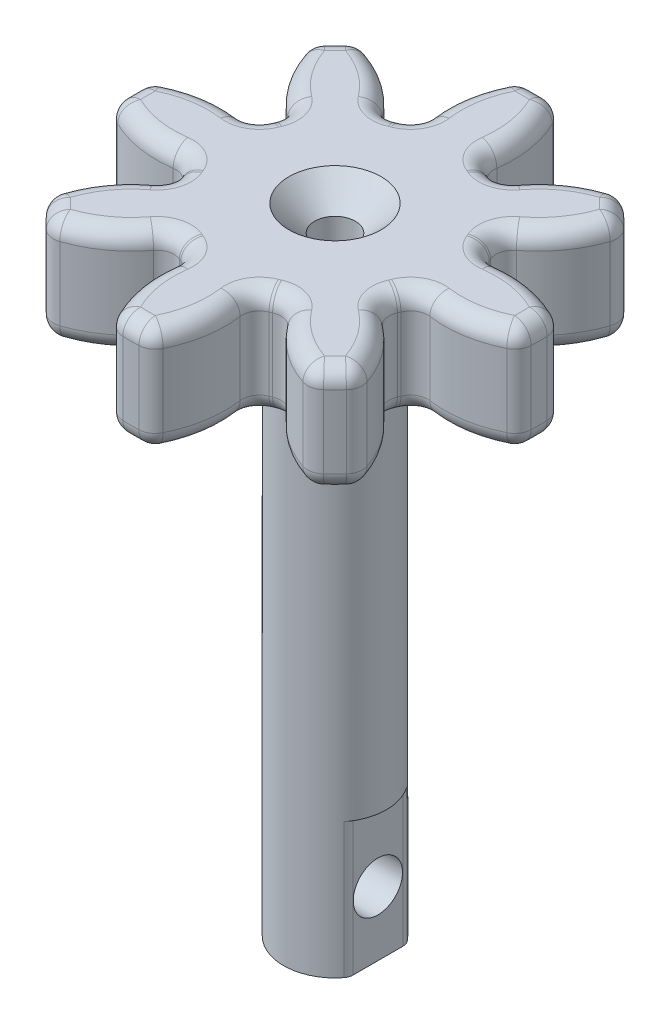
SolidWorks part; units mm, degrees
ref_plane "Front Plane" through (0, 0, 0) normal (0, 0, 1) x (1, 0, 0)
ref_plane "Top Plane" through (0, 0, 0) normal (0, 1, 0) x (1, 0, 0)
ref_plane "Right Plane" through (0, 0, 0) normal (1, 0, 0) x (0, 0, -1)
sketch "Sketch2" plane through (0, 0, 0) normal (0, 1, 0) x (1, 0, 0)
  line L0 (1.5575, 7.479) -> (0, 0) construction
  line L1 (1.5575, 7.479) -> (1.9249, 4.9409) construction
  line L2 (-1.4311, 5.3411) -> (0, 0) construction
  line L3 (0, 0) -> (1.4311, 5.3411) construction
  line L4 (-6.7384, 6.7384) -> (0, 0) construction
  line L5 (0, 0) -> (-2.7648, 4.7887) construction
  circle A0 centre (0, 0) radius 5.5295 construction
  circle A1 centre (0, 0) radius 9.5295 construction
  arc A2 (1.4311, 5.3411) -> (0.8301, 9.4933) centre (-3.7048, 6.7173) ccw
  arc A3 (-1.4311, 5.3411) -> (-0.8301, 9.4933) centre (3.7048, 6.7173) cw
  arc A4 (0.8301, 9.4933) -> (-0.8301, 9.4933) centre (0, 0) ccw
  arc A5 (1.4311, 5.3411) -> (2.7648, 4.7887) centre (0, 0) cw
  arc A6 (4.7887, 2.7648) -> (5.3411, 1.4311) centre (0, 0) cw
  arc A7 (4.7887, 2.7648) -> (7.2997, 6.1258) centre (2.1302, 7.3695) ccw
  arc A8 (7.2997, 6.1258) -> (6.1258, 7.2997) centre (0, 0) ccw
  arc A9 (2.7648, 4.7887) -> (6.1258, 7.2997) centre (7.3695, 2.1302) cw
  arc A10 (5.3411, -1.4311) -> (4.7887, -2.7648) centre (0, 0) cw
  arc A11 (5.3411, -1.4311) -> (9.4933, -0.8301) centre (6.7173, 3.7048) ccw
  arc A12 (9.4933, -0.8301) -> (9.4933, 0.8301) centre (0, 0) ccw
  arc A13 (5.3411, 1.4311) -> (9.4933, 0.8301) centre (6.7173, -3.7048) cw
  arc A14 (2.7648, -4.7887) -> (1.4311, -5.3411) centre (0, 0) cw
  arc A15 (2.7648, -4.7887) -> (6.1258, -7.2997) centre (7.3695, -2.1302) ccw
  arc A16 (6.1258, -7.2997) -> (7.2997, -6.1258) centre (0, 0) ccw
  arc A17 (4.7887, -2.7648) -> (7.2997, -6.1258) centre (2.1302, -7.3695) cw
  arc A18 (-1.4311, -5.3411) -> (-2.7648, -4.7887) centre (0, 0) cw
  arc A19 (-1.4311, -5.3411) -> (-0.8301, -9.4933) centre (3.7048, -6.7173) ccw
  arc A20 (-0.8301, -9.4933) -> (0.8301, -9.4933) centre (0, 0) ccw
  arc A21 (1.4311, -5.3411) -> (0.8301, -9.4933) centre (-3.7048, -6.7173) cw
  arc A22 (-4.7887, -2.7648) -> (-5.3411, -1.4311) centre (0, 0) cw
  arc A23 (-4.7887, -2.7648) -> (-7.2997, -6.1258) centre (-2.1302, -7.3695) ccw
  arc A24 (-7.2997, -6.1258) -> (-6.1258, -7.2997) centre (0, 0) ccw
  arc A25 (-2.7648, -4.7887) -> (-6.1258, -7.2997) centre (-7.3695, -2.1302) cw
  arc A26 (-5.3411, 1.4311) -> (-4.7887, 2.7648) centre (0, 0) cw
  arc A27 (-5.3411, 1.4311) -> (-9.4933, 0.8301) centre (-6.7173, -3.7048) ccw
  arc A28 (-9.4933, 0.8301) -> (-9.4933, -0.8301) centre (0, 0) ccw
  arc A29 (-5.3411, -1.4311) -> (-9.4933, -0.8301) centre (-6.7173, 3.7048) cw
  arc A30 (-2.7648, 4.7887) -> (-1.4311, 5.3411) centre (0, 0) cw
  arc A31 (-2.7648, 4.7887) -> (-6.1258, 7.2997) centre (-7.3695, 2.1302) ccw
  arc A32 (-6.1258, 7.2997) -> (-7.2997, 6.1258) centre (0, 0) ccw
  arc A33 (-4.7887, 2.7648) -> (-7.2997, 6.1258) centre (-2.1302, 7.3695) cw
  arc A34 (6.3897, 4.1871) -> (1.5575, 7.479) centre (0, 0) ccw construction
  arc A35 (-1.0542, 3.9343) -> (-2.0366, 3.5274) centre (0, 0) ccw construction
  arc A36 (-2.0366, 3.5274) -> (-2.8801, 2.8801) centre (0, 0) ccw construction
  point P12 (0, 9.5295)
  point P68 (0, 0)
  dimension "D2" = 4
  dimension "D1" = 20
  dimension "D4" = 6
  dimension "D3" = 8
extrude "Boss-Extrude1" add sketch "Sketch2" along normal blind 5
fillet "Fillet3" radius 0.8 96 edges at (1.4311, 2.5, -5.3411) (0.8301, 2.5, -9.4933) (-0.8301, 2.5, -9.4933) (-1.4311, 2.5, -5.3411) (-2.7648, 2.5, -4.7887) (-6.1258, 2.5, -7.2997) (-7.2997, 2.5, -6.1258) (-4.7887, 2.5, -2.7648) (-5.3411, 2.5, -1.4311) (-9.4933, 2.5, -0.8301) (-9.4933, 2.5, 0.8301) (-5.3411, 2.5, 1.4311) (-4.7887, 2.5, 2.7648) (-7.2997, 2.5, 6.1258) (-6.1258, 2.5, 7.2997) (-2.7648, 2.5, 4.7887) (-1.4311, 2.5, 5.3411) (-0.8301, 2.5, 9.4933) (0.8301, 2.5, 9.4933) (1.4311, 2.5, 5.3411) (2.7648, 2.5, 4.7887) (6.1258, 2.5, 7.2997) (7.2997, 2.5, 6.1258) (4.7887, 2.5, 2.7648) (5.3411, 2.5, 1.4311) (9.4933, 2.5, 0.8301) (9.4933, 2.5, -0.8301) (5.3411, 2.5, -1.4311) (4.7887, 2.5, -2.7648) (7.2997, 2.5, -6.1258) (6.1258, 2.5, -7.2997) (2.7648, 2.5, -4.7887) (4.1871, 5, -6.3897) (6.7384, 5, -6.7384) (6.3897, 5, -4.1871) (5.1086, 5, -2.1161) (7.479, 5, -1.5575) (9.5295, 5, 0) (7.479, 5, 1.5575) (5.1086, 5, 2.1161) (6.3897, 5, 4.1871) (6.7384, 5, 6.7384) (4.1871, 5, 6.3897) (2.1161, 5, 5.1086) (1.5575, 5, 7.479) (0, 5, 9.5295) (-1.5575, 5, 7.479) (-2.1161, 5, 5.1086) (-4.1871, 5, 6.3897) (-6.7384, 5, 6.7384) (-6.3897, 5, 4.1871) (-5.1086, 5, 2.1161) (-7.479, 5, 1.5575) (-9.5295, 5, 0) (-7.479, 5, -1.5575) (-5.1086, 5, -2.1161) (-6.3897, 5, -4.1871) (-6.7384, 5, -6.7384) (-4.1871, 5, -6.3897) (-2.1161, 5, -5.1086) (-1.5575, 5, -7.479) (0, 5, -9.5295) (1.5575, 5, -7.479) (2.1161, 5, -5.1086) (4.1871, 0, -6.3897) (6.7384, 0, -6.7384) (6.3897, 0, -4.1871) (5.1086, 0, -2.1161) (7.479, 0, -1.5575) (9.5295, 0, 0) (7.479, 0, 1.5575) (5.1086, 0, 2.1161) (6.3897, 0, 4.1871) (6.7384, 0, 6.7384) (4.1871, 0, 6.3897) (2.1161, 0, 5.1086) (1.5575, 0, 7.479) (0, 0, 9.5295) (-1.5575, 0, 7.479) (-2.1161, 0, 5.1086) (-4.1871, 0, 6.3897) (-6.7384, 0, 6.7384) (-6.3897, 0, 4.1871) (-5.1086, 0, 2.1161) (-7.479, 0, 1.5575) (-9.5295, 0, 0) (-7.479, 0, -1.5575) (-5.1086, 0, -2.1161) (-6.3897, 0, -4.1871) (-6.7384, 0, -6.7384) (-4.1871, 0, -6.3897) (-2.1161, 0, -5.1086) (-1.5575, 0, -7.479) (0, 0, -9.5295) (1.5575, 0, -7.479) (2.1161, 0, -5.1086)
sketch "Sketch4" plane through (0, 0, 0) normal (0, -1, 0) x (1, 0, 0)
  circle A0 centre (0, 0) radius 2.4
  dimension "D1" = 4.8
extrude "Boss-Extrude2" add sketch "Sketch4" along normal blind 18.3
sketch "Sketch5" plane through (0, -18.3, 0) normal (0, -1, 0) x (1, 0, 0)
  line L5 (-2, 1.3266) -> (-2, -1.3266)
  line L7 (2, -1.3266) -> (2, 1.3266)
  circle A1 centre (0, 0) radius 2.4 construction
  circle A2 centre (0, 0) radius 2.4 construction
  arc A3 (2, 1.3266) -> (-2, 1.3266) centre (0, 0) ccw
  arc A5 (-2, -1.3266) -> (2, -1.3266) centre (0, 0) ccw
  point P0 (0, 0)
  dimension "D1" = 4
extrude "Boss-Extrude3" add sketch "Sketch5" along normal blind 6.3
fillet "Fillet4" radius 0.5 4 edges at (-2, -21.45, 1.3266) (-2, -21.45, -1.3266) (2, -21.45, 1.3266) (2, -21.45, -1.3266)
sketch "Sketch6" plane through (2, 0, 0) normal (1, 0, 0) x (0, 0, -1)
  line L0 (-1.4731, -18.3) -> (1.4731, -18.3) construction
  line L1 (1.1662, -24.6) -> (-1.1662, -24.6) construction
  circle A0 centre (0, -21.6) radius 1.15
  point P4 (0, -18.3)
  dimension "D1" = 2.3
  dimension "D2" = 3
extrude "Cut-Extrude1" cut sketch "Sketch6" against normal blind 10
sketch "Sketch7" plane through (0, 5, 0) normal (0, 1, 0) x (1, 0, 0)
  circle A0 centre (0, 0) radius 0.95
  dimension "D1" = 1.9
extrude "Cut-Extrude2" cut sketch "Sketch7" against normal blind 22
chamfer "Chamfer1" distance 1.2 angle 45 1 edges at (0, 5, 0.95)
